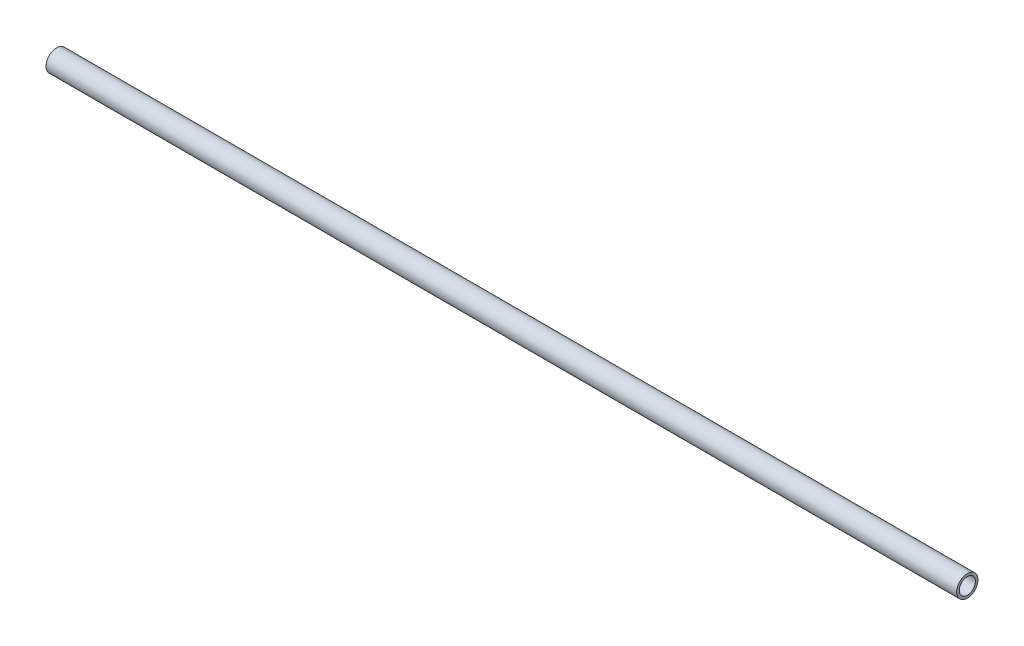
SolidWorks part; units mm, degrees
ref_plane "Front Plane" through (0, 0, 0) normal (0, 0, 1) x (1, 0, 0)
ref_plane "Top Plane" through (0, 0, 0) normal (0, 1, 0) x (1, 0, 0)
ref_plane "Right Plane" through (0, 0, 0) normal (1, 0, 0) x (0, 0, -1)
ref_axis "Axis1" through (-4.5, 0, 0) along (1, 0, 0)
sketch "Sketch1" plane through (0, 0, 0) normal (1, 0, 0) x (0, 0, -1)
  circle A0 centre (0, 0) radius 0.8001
  circle A1 centre (0, 0) radius 1.0541
  dimension "D1" = 1.6002
  dimension "D2" = 2.1082
extrude "Boss-Extrude1" add sketch "Sketch1" along normal blind 90
sketch "Sketch2" plane through (0, 0, 0) normal (-1, 0, 0) x (0, 0, 1)
  line L0 (0, 0) -> (0, 0.6106) construction
  line L2 (-0.304, 0.6106) -> (-0.304, 1.0992)
  line L3 (-0.304, 1.0992) -> (0.304, 1.0992)
  line L4 (0.304, 1.0992) -> (0.304, 0.6106)
  arc A0 (-0.304, 0.6106) -> (0.304, 0.6106) centre (0, 0.6106) ccw
  dimension "D1" = 0.608
extrude "Cut-Extrude1" [suppressed] cut sketch "Sketch2" against normal blind 1
sketch "Sketch3" plane through (0, 0, 0) normal (0, 0, 1) x (1, 0, 0)
  line L0 (1.0797, 0) -> (4.2297, 0) construction
  line L1 (1.0797, 0.7937) -> (4.2297, 0.7937)
  line L2 (1.0797, -0.7937) -> (4.2297, -0.7937)
  arc A0 (1.0797, 0.7937) -> (1.0797, -0.7937) centre (1.0797, 0) ccw
  arc A1 (4.2297, -0.7937) -> (4.2297, 0.7937) centre (4.2297, 0) ccw
  point P3 (2.6547, 0)
  dimension "D1" = 0.7937
  dimension "D2" = 3.15
extrude "Cut-Extrude2" cut sketch "Sketch3" against normal blind 10
equation "\"Do\"=8.5mm"
equation "\"Lo\"=10"
equation "\"screw_diam\"= 3.5mm"
equation "\"wheel_Do\"=12.5mm"
equation "\"wheel_thickness\"=4mm"
equation "\"Collet_diameter\"=4.3"
equation "\"clearance\"= 0.5mm"
equation "\"handle_body_width\"= 10mm"
equation "\"finger_diameter\"=35"
equation "\"collet_lid_diameter\"=10"
equation "\"screw_cap_diam\"=5.15"
equation "\"handle_thickness\"=12.5mm"
equation "\"post_hole_diam\"=2"
equation "\"roll_rod_diam\"= 6.5 "
equation "\"roll_rod_length\"=6.6"
equation "\"disc_diam\"=5"
equation "\"disc_width\"=1.5"
equation "\"arm_width\"=5"
equation "\"arm_thickness\"=4.5"
equation "\"wheel_total_diam\"=30"
equation "\"spring_diam\"=4.1"
equation "\"collet_length\"= 18.75mm"
equation "\"tip_length\"= 40mm"
equation "\"cable_tube_OD\"=0.508"
equation "\"D1@Sketch2\"=\"cable_tube_OD\"+0.1"
